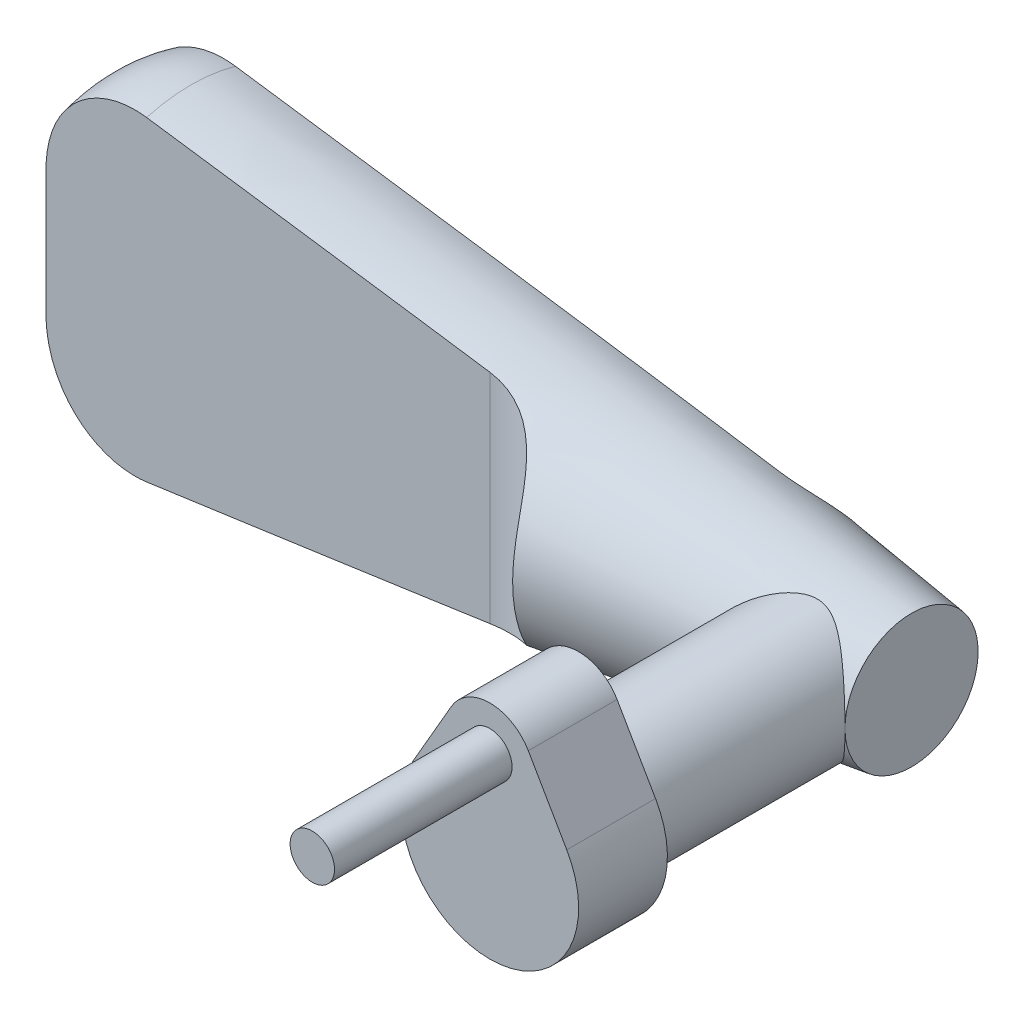
SolidWorks part; units mm, degrees
ref_plane "Front Plane" through (0, 0, 0) normal (0, 0, 1) x (1, 0, 0)
ref_plane "Top Plane" through (0, 0, 0) normal (0, 1, 0) x (1, 0, 0)
ref_plane "Right Plane" through (0, 0, 0) normal (1, 0, 0) x (0, 0, -1)
sketch "Sketch2" plane through (0, 0, 0) normal (0, 0, 1) x (1, 0, 0)
  line L0 (0, 0) -> (0, 25.4) construction
  line L1 (-10.9985, 31.75) -> (-21.997, 12.7)
  line L2 (10.9985, 31.75) -> (21.997, 12.7)
  circle A0 centre (0, 0) radius 25.4 construction
  circle A1 centre (0, 25.4) radius 12.7 construction
  arc A2 (-21.997, 12.7) -> (21.997, 12.7) centre (0, 0) ccw
  arc A3 (-10.9985, 31.75) -> (10.9985, 31.75) centre (0, 25.4) cw
  point P11 (0, 0)
  dimension "D1" = 25.4
  dimension "D2" = 25.4
  dimension "D3" = 12.7
extrude "Boss-Extrude1" add sketch "Sketch2" against normal blind 25.4
sketch "Sketch3" plane through (0, 0, 0) normal (0, 0, 1) x (1, 0, 0)
  line L0 (0, 25.4) -> (0, 0) construction
  circle A0 centre (0, 25.4) radius 6.35
  dimension "D1" = 12.7
  dimension "D2" = 25.4
extrude "Boss-Extrude2" add sketch "Sketch3" along normal blind 50.8
sketch "Sketch4" plane through (0, 0, 0) normal (0, 0, 1) x (1, 0, 0)
  circle A0 centre (0, 0) radius 19.05
  dimension "D1" = 38.1
extrude "Boss-Extrude3" add sketch "Sketch4" against normal blind 101.6
sketch "Sketch5" plane through (0, 0, 0) normal (0, -1, 0) x (0, 0, -1)
  line L4 (101.6, 19.05) -> (120.65, 19.05)
  line L6 (120.65, 19.05) -> (152.4, -215.9)
  line L8 (152.4, -215.9) -> (101.6, -215.9)
  line L9 (101.6, -215.9) -> (101.6, 19.05)
  dimension "D1" = 19.05
  dimension "D2" = 234.95
  dimension "D3" = 50.8
revolve "Revolve3" add sketch "Sketch5" angle 360 about L9
sketch "Sketch6" plane through (0, 0, 0) normal (0, 1, 0) x (1, 0, 0)
  line L0 (19.05, 101.6) -> (-215.9, 101.6) construction
  line L1 (19.05, 82.55) -> (19.05, 120.65) construction
  line L2 (-215.9, 152.4) -> (-215.9, 50.8) construction
  line L4 (-280.4391, 214.4046) -> (-6.35, 214.4046)
  line L5 (-280.4391, 214.4046) -> (-280.4391, 114.3)
  line L6 (-280.4391, 114.3) -> (-6.35, 114.3)
  line L7 (-6.35, 214.4046) -> (-6.35, 114.3)
  line L8 (-280.4391, 88.9) -> (-63.5, 88.9)
  line L9 (-280.4391, 88.9) -> (-280.4391, 9.0043)
  line L10 (-280.4391, 9.0043) -> (-63.5, 9.0043)
  line L11 (-63.5, 88.9) -> (-63.5, 9.0043)
  dimension "D1" = 12.7
  dimension "D2" = 12.7
  dimension "D3" = 63.5
  dimension "D4" = 6.35
extrude "Cut-Extrude1" cut sketch "Sketch6" against normal mid plane 234.95
fillet "Fillet1" radius 25.4 4 edges at (-63.5, 0, -88.9) (-215.9, 50.8, -101.6) (-215.9, -50.8, -101.6) (-6.35, 0, -114.3)
